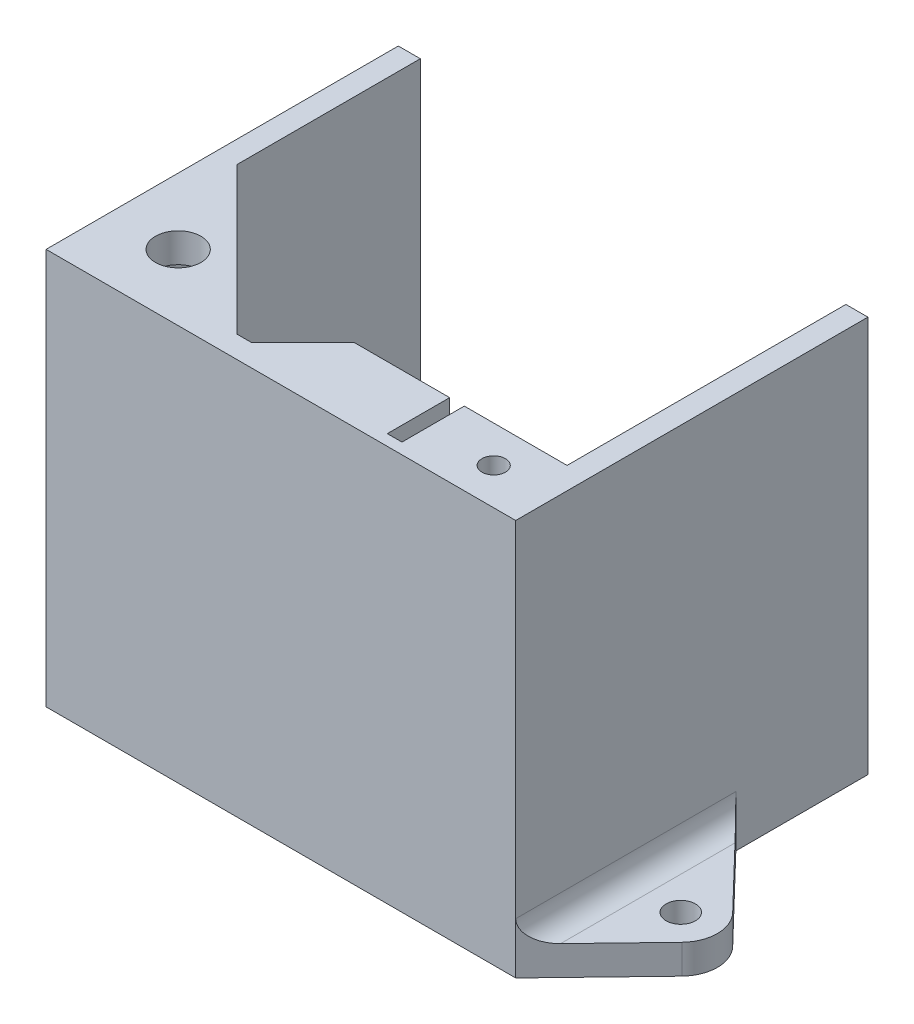
SolidWorks part; units mm, degrees
ref_plane "Płaszczyzna przednia" through (0, 0, 0) normal (0, 0, 1) x (1, 0, 0)
ref_plane "Płaszczyzna górna" through (0, 0, 0) normal (0, 1, 0) x (1, 0, 0)
ref_plane "Płaszczyzna prawa" through (0, 0, 0) normal (1, 0, 0) x (0, 0, -1)
sketch "Sketch1" plane through (0, 0, 0) normal (0, 1, 0) x (1, 0, 0)
  line L1 (-32, 24) -> (32, 24)
  line L2 (-32, 24) -> (-32, -24)
  line L3 (-32, -24) -> (32, -24)
  line L4 (32, 24) -> (32, -24)
  line L5 (-32, 24) -> (32, -24) construction
  line L6 (-32, -24) -> (32, 24) construction
  point P0 (0, 0)
  dimension "D1" = 64
  dimension "D2" = 48
extrude "Boss-Extrude1" add sketch "Sketch1" along normal blind 4
sketch "Sketch2" plane through (0, 0, 0) normal (0, -1, 0) x (1, 0, 0)
  line L9 (-20.6514, -16) -> (-22.3257, -13.1)
  line L10 (-22.3257, -13.1) -> (-25.6743, -13.1)
  line L11 (-25.6743, -13.1) -> (-27.3486, -16)
  line L12 (-27.3486, -16) -> (-25.6743, -18.9)
  line L13 (-25.6743, -18.9) -> (-22.3257, -18.9)
  line L14 (-22.3257, -18.9) -> (-20.6514, -16)
  line L15 (-32, -24) -> (-32, 24) construction
  line L16 (32, -24) -> (-32, -24) construction
  circle A0 centre (-24, -16) radius 2.9 construction
  dimension "D3" = 5.8
  dimension "D1" = 8
  dimension "D2" = 8
extrude "Cut-Extrude1" cut sketch "Sketch2" against normal blind 2.4
sketch "Sketch4" plane through (0, 0, 0) normal (0, -1, 0) x (1, 0, 0)
  line L0 (-32, -24) -> (-32, 24) construction
  line L1 (9.3486, 10) -> (7.6743, 12.9)
  line L2 (7.6743, 12.9) -> (4.3257, 12.9)
  line L3 (4.3257, 12.9) -> (2.6514, 10)
  line L4 (2.6514, 10) -> (4.3257, 7.1)
  line L5 (4.3257, 7.1) -> (7.6743, 7.1)
  line L6 (7.6743, 7.1) -> (9.3486, 10)
  line L8 (32, -24) -> (-32, -24) construction
  circle A0 centre (6, 10) radius 2.9 construction
  dimension "D3" = 5.8
  dimension "D1" = 38
  dimension "D2" = 34
extrude "Cut-Extrude2" cut sketch "Sketch4" against normal blind 2.4
sketch "Sketch6" plane through (0, 4, 0) normal (0, 1, 0) x (1, 0, 0)
  line L0 (-29, 21) -> (-29, 24)
  line L1 (-32, 24) -> (32, 24)
  line L2 (-32, 24) -> (-32, -24)
  line L3 (-32, -24) -> (32, -24)
  line L4 (32, 24) -> (32, -24)
  line L5 (-29, 21) -> (29, 21)
  line L6 (-29, 21) -> (-29, -21)
  line L7 (-29, -21) -> (29, -21)
  line L8 (29, 21) -> (29, -21)
  line L9 (-29, 21) -> (29, -21) construction
  line L10 (-29, -21) -> (29, 21) construction
  line L11 (29, 21) -> (29, 24)
  point P6 (0, 0)
  line M1 (32, -24) -> (32, 24)
  line M2 (32, 24) -> (-32, 24)
  line M3 (-32, 24) -> (-32, -24)
  line M4 (-32, -24) -> (32, -24)
  dimension "D1" = 58
  dimension "D2" = 42
extrude "Boss-Extrude3" add sketch "Sketch6" along normal blind 50 contours L11 L8 L7 L6 L0 M2 M3 M4 M1 region at (-29.8, 4, 0)
sketch "Sketch9" plane through (0, 4, 0) normal (0, 1, 0) x (1, 0, 0)
  line L0 (1, -13) -> (-7, -21)
  line L3 (29, -13) -> (1, -13)
  line L5 (-29, -21) -> (29, -21) construction
  line L6 (-7, -21) -> (29, -21)
  line L7 (1, -13) -> (-7, -21)
  line L9 (29, -21) -> (29, -13)
  line M3 (29, -21) -> (29, 24)
  line M6 (-29, -21) -> (29, -21)
  dimension "D1" = 8
  dimension "D2" = 8
  dimension "D3" = 28
extrude "Boss-Extrude4" add sketch "Sketch9" along normal blind 50 contours L3 L0 M3 M6 region at (12.9167, 4, 17.1667)
sketch "Sketch10" plane through (0, 0, 13) normal (0, 0, -1) x (-1, 0, 0)
  line L0 (-29, 54) -> (-29, 4) construction
  line L1 (-27, 39) -> (-1, 39)
  line L2 (-27, 39) -> (-27, 13)
  line L3 (-27, 13) -> (-1, 13)
  line L4 (-1, 39) -> (-1, 13)
  line L5 (-27, 39) -> (-1, 13) construction
  line L6 (-27, 13) -> (-1, 39) construction
  line L7 (-14, 39) -> (-14, 54) construction
  line L9 (-29, 54) -> (-1, 54) construction
  line L15 (-14.9986, 39) -> (-13.0014, 39)
  line L16 (-14.9986, 39) -> (-14.9986, 54)
  line L17 (-14.9986, 54) -> (-13.0014, 54)
  line L18 (-13.0014, 39) -> (-13.0014, 54)
  line L19 (-14.9986, 39) -> (-13.0014, 54) construction
  line L20 (-14.9986, 54) -> (-13.0014, 39) construction
  point P0 (-14, 26)
  point P9 (-14, 46.5)
  line M4 (-1, 4) -> (-1, 54)
  line M5 (-1, 54) -> (-29, 54)
  dimension "D1" = 26
  dimension "D2" = 26
  dimension "D3" = 15
  dimension "D5" = 28
extrude "Cut-Extrude4" cut sketch "Sketch10" against normal blind 9.5 contours L2 L3 L1 M4 | L1 M5 region at (14, 26, 13) region at (14, 46.5, 13)
sketch "Sketch13" plane through (0, 54, 0) normal (0, 1, 0) x (1, 0, 0)
  line L1 (29, -13) -> (-7.9463, -13)
  line L2 (29, -13) -> (29, -14)
  line L3 (29, -14) -> (-7.9463, -14)
  line L4 (-7.9463, -13) -> (-7.9463, -14)
  dimension "D1" = 1
extrude "Cut-Extrude6" cut sketch "Sketch13" against normal blind 32
sketch "Sketch15" plane through (0, 54, 0) normal (0, 1, 0) x (1, 0, 0)
  line L0 (-29, -1) -> (-9, -21)
  line L5 (-29, 24) -> (-29, -21) construction
  line L6 (-29, -21) -> (-7, -21) construction
  line L7 (-29, 24) -> (-29, -21) construction
  line L8 (-29, -1) -> (-29, -21)
  line L9 (-29, -21) -> (-9, -21)
  line L10 (-32, 24) -> (-32, -24) construction
  line L11 (-32, -24) -> (32, -24) construction
  circle A0 centre (-23, -15) radius 3.1
  dimension "D3" = 9
  dimension "D1" = 20
  dimension "D2" = 20
  dimension "D4" = 9
extrude "Boss-Extrude5" add sketch "Sketch15" against normal blind 4
sketch "Sketch17" plane through (0, 54, 0) normal (0, 1, 0) x (1, 0, 0)
  line L0 (32, -24) -> (32, 24) construction
  line L7 (-32, -24) -> (32, -24) construction
  line L8 (24, -19) -> (24, -24) construction
  line L9 (24, -19) -> (32, -19) construction
  line L11 (24, -15.6514) -> (21.1, -17.3257)
  line L12 (21.1, -17.3257) -> (21.1, -20.6743)
  line L13 (21.1, -20.6743) -> (24, -22.3486)
  line L14 (24, -22.3486) -> (26.9, -20.6743)
  line L15 (26.9, -20.6743) -> (26.9, -17.3257)
  line L16 (26.9, -17.3257) -> (24, -15.6514)
  circle A0 centre (24, -19) radius 2.9 construction
  dimension "D1" = 8
  dimension "D3" = 5.8
  dimension "D2" = 5
extrude "Cut-Extrude7" cut sketch "Sketch17" against normal blind 7
sketch "Sketch18" plane through (0, 0, 14) normal (0, 0, -1) x (-1, 0, 0)
  line L0 (-14.9986, 54) -> (-29, 54) construction
  line L1 (-26.9, 49.6) -> (-21.1, 49.6)
  line L2 (-26.9, 49.6) -> (-26.9, 47)
  line L3 (-26.9, 47) -> (-21.1, 47)
  line L4 (-21.1, 49.6) -> (-21.1, 47)
  line L5 (-32, 54) -> (-32, 0) construction
  point P6 (-24, 49.6)
  dimension "D1" = 7
  dimension "D2" = 2.6
  dimension "D3" = 5.8
  dimension "D4" = 8
extrude "Cut-Extrude8" cut sketch "Sketch18" against normal blind 5
sketch "Sketch19" plane through (0, 54, 0) normal (0, 1, 0) x (1, 0, 0)
  line L0 (25.6, -19) -> (22.4, -19) construction
  line L6 (22.4, -19) -> (24, -17.4) construction
  line L8 (24, -17.4) -> (24, -20.6) construction
  line L10 (20.7023, -15.4012) -> (27.2977, -15.4012)
  line L11 (20.7023, -15.4012) -> (20.7023, -22.5988)
  line L12 (20.7023, -22.5988) -> (27.2977, -22.5988)
  line L13 (27.2977, -15.4012) -> (27.2977, -22.5988)
  line L14 (20.7023, -22.5988) -> (27.2977, -22.5988)
  line L15 (20.7023, -22.5988) -> (20.7023, -15.4012)
  line L16 (20.7023, -15.4012) -> (27.2977, -15.4012)
  line L17 (27.2977, -22.5988) -> (27.2977, -15.4012)
  line L18 (20.7023, -22.5988) -> (27.2977, -15.4012) construction
  line L19 (20.7023, -15.4012) -> (27.2977, -22.5988) construction
  circle A0 centre (24, -19) radius 1.6
  line M1 (24, -15.6514) -> (26.9, -17.3257)
  line M2 (26.9, -17.3257) -> (26.9, -20.6743)
  line M3 (26.9, -20.6743) -> (24, -22.3486)
  line M4 (24, -22.3486) -> (21.1, -20.6743)
  line M5 (21.1, -20.6743) -> (21.1, -17.3257)
  line M6 (21.1, -17.3257) -> (24, -15.6514)
extrude "Boss-Extrude8" add sketch "Sketch19" against normal blind 4.4 contours A0 M1 M6 M5 M4 M3 M2 region at (25.4057, 54, 16.5653)
fillet "Fillet1" radius 1.5 2 edges at (-29, 50, 11) (-19, 50, 21)
sketch "Sketch20" plane through (0, 0, 0) normal (0, -1, 0) x (1, 0, 0)
  line L0 (32, 24) -> (43.1021, 12.4677)
  line L1 (39.5, 9) -> (32, 9) construction
  line L2 (32, -6) -> (43.1021, 5.5323)
  line L3 (-32, -24) -> (-42.9789, -14.5912)
  line L4 (32, -6) -> (32, 24)
  line L6 (-32, 2) -> (-32, -24)
  line L8 (-39.5, -11) -> (-32, -11) construction
  line L9 (-32, 2) -> (-42.9789, -7.4088)
  line L10 (-20.8246, -16) -> (-22.4123, -13.25) construction
  line L11 (-22.4123, -18.75) -> (-20.8246, -16) construction
  line L12 (-25.5877, -18.75) -> (-22.4123, -18.75) construction
  line L13 (-27.1754, -16) -> (-25.5877, -18.75) construction
  line L14 (-25.5877, -13.25) -> (-27.1754, -16) construction
  line L15 (-22.4123, -13.25) -> (-25.5877, -13.25) construction
  line L16 (9.1754, 10) -> (7.5877, 12.75) construction
  line L17 (7.5877, 7.25) -> (9.1754, 10) construction
  line L18 (4.4123, 7.25) -> (7.5877, 7.25) construction
  line L19 (2.8246, 10) -> (4.4123, 7.25) construction
  line L20 (4.4123, 12.75) -> (2.8246, 10) construction
  line L21 (7.5877, 12.75) -> (4.4123, 12.75) construction
  line L22 (-22.3257, -13.1) -> (-25.6743, -13.1) construction
  line L23 (-20.6514, -16) -> (-22.3257, -13.1) construction
  line L24 (-22.3257, -13.1) -> (-25.6743, -13.1) construction
  line L25 (-20.6514, -16) -> (-22.3257, -13.1) construction
  line L26 (32, -24) -> (32, 24)
  line L27 (32, 24) -> (-32, 24)
  line L28 (-32, 24) -> (-32, -24)
  line L29 (-32, -24) -> (32, -24)
  line L30 (32, -6) -> (32, 24)
  line L32 (-32, 2) -> (-32, -24)
  line L36 (9.3486, 10) -> (7.6743, 12.9)
  line L37 (7.6743, 7.1) -> (9.3486, 10)
  line L38 (4.3257, 7.1) -> (7.6743, 7.1)
  line L39 (2.6514, 10) -> (4.3257, 7.1)
  line L40 (4.3257, 12.9) -> (2.6514, 10)
  line L41 (7.6743, 12.9) -> (4.3257, 12.9)
  line L42 (9.3486, 10) -> (7.6743, 12.9) construction
  line L43 (7.6743, 7.1) -> (9.3486, 10) construction
  line L44 (4.3257, 7.1) -> (7.6743, 7.1) construction
  line L45 (2.6514, 10) -> (4.3257, 7.1) construction
  line L46 (4.3257, 12.9) -> (2.6514, 10) construction
  line L47 (7.6743, 12.9) -> (4.3257, 12.9) construction
  line L48 (-20.6514, -16) -> (-22.3257, -13.1)
  line L49 (-22.3257, -18.9) -> (-20.6514, -16)
  line L50 (-25.6743, -18.9) -> (-22.3257, -18.9)
  line L51 (-27.3486, -16) -> (-25.6743, -18.9)
  line L52 (-25.6743, -13.1) -> (-27.3486, -16)
  line L53 (-22.3257, -13.1) -> (-25.6743, -13.1)
  line L54 (-20.6514, -16) -> (-22.3257, -13.1) construction
  line L55 (-22.3257, -18.9) -> (-20.6514, -16) construction
  line L56 (-25.6743, -18.9) -> (-22.3257, -18.9) construction
  line L57 (-27.3486, -16) -> (-25.6743, -18.9) construction
  line L58 (-25.6743, -13.1) -> (-27.3486, -16) construction
  line L59 (-22.3257, -13.1) -> (-25.6743, -13.1) construction
  circle A0 centre (39.5, 9) radius 2
  circle A1 centre (-39.5, -11) radius 2
  arc A2 (43.1021, 5.5323) -> (43.1021, 12.4677) centre (39.5, 9) ccw
  arc A3 (-42.5162, -7.0122) -> (-42.5162, -14.9878) centre (-39.5, -11) ccw
  dimension "D1" = 0
  dimension "D2" = 0
  dimension "D3" = 0
extrude "Boss-Extrude9" add sketch "Sketch20" against normal blind 4 contours L9 A3 L3 L23 A1 | L2 A2 L0 L4 A0 region at (36.4432, 0, 9) region at (-36.5396, 0, -11)
fillet "Fillet2" radius 3 2 edges at (-32, 4, -11) (32, 4, 9)
sketch "Sketch22" plane through (0, 2.4, 0) normal (0, -1, 0) x (1, 0, 0)
  line L0 (4.3257, 12.9) -> (7.6743, 7.1) construction
  line L1 (7.6743, 7.1) -> (7.6743, 12.9) construction
  line L2 (7.6743, 12.9) -> (4.3257, 7.1) construction
  line L3 (-25.6743, -18.9) -> (-22.3257, -13.1) construction
  line L4 (-22.3257, -13.1) -> (-22.3257, -18.9) construction
  line L5 (-25.6743, -13.1) -> (-22.3257, -18.9) construction
  circle A0 centre (-24, -16) radius 1.65
  circle A1 centre (6, 10) radius 1.65
  dimension "D1" = 3.3
  dimension "D2" = 3.3
extrude "Cut-Extrude9" cut sketch "Sketch22" against normal blind 2
